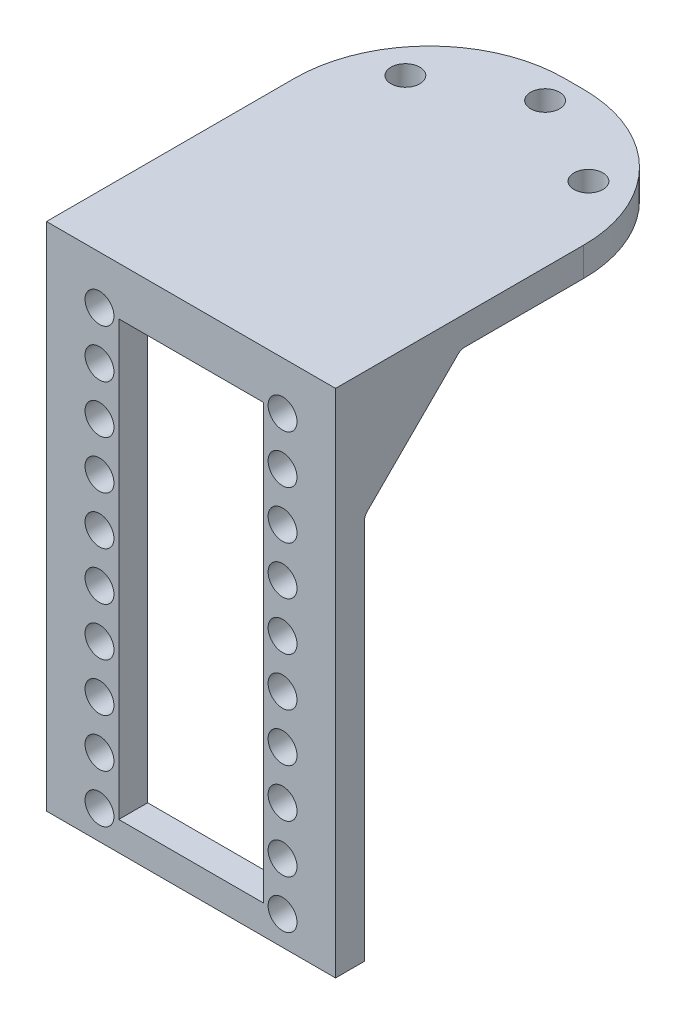
SolidWorks part; units mm, degrees
ref_plane "Front Plane" through (0, 0, 0) normal (0, 0, 1) x (1, 0, 0)
ref_plane "Top Plane" through (0, 0, 0) normal (0, 1, 0) x (1, 0, 0)
ref_plane "Right Plane" through (0, 0, 0) normal (1, 0, 0) x (0, 0, -1)
sketch "Sketch1" plane through (0, 0, 0) normal (1, 0, 0) x (0, 0, -1)
  line L0 (16.1753, 7.5418) -> (16.1753, 4.5418)
  line L1 (16.1753, 4.5418) -> (-15.8247, 4.5418)
  line L2 (-15.8247, 4.5418) -> (-15.8247, -45.4582)
  line L3 (-15.8247, -45.4582) -> (-18.8247, -45.4582)
  line L4 (-18.8247, -45.4582) -> (-18.8247, 7.5418)
  line L5 (-18.8247, 7.5418) -> (16.1753, 7.5418)
  dimension "D1" = 35
  dimension "D2" = 3
  dimension "D3" = 3
  dimension "D4" = 50
extrude "Boss-Extrude1" add sketch "Sketch1" against normal blind 30
sketch "Sketch2" plane through (0, 7.5418, 0) normal (0, 1, 0) x (1, 0, 0)
  line L0 (-30, 16.1753) -> (-30, -18.8247) construction
  line L1 (-30, 16.1753) -> (0, 16.1753) construction
  circle A0 centre (-5.5, 12.9253) radius 1.5
  circle A1 centre (-24.5, 12.9253) radius 1.5
  point P4 (0, 0)
  dimension "D1" = 3
  dimension "D2" = 19
  dimension "D3" = 5.5
  dimension "D4" = 3.25
extrude "Cut-Extrude1" cut sketch "Sketch2" against normal up to surface (3 mm away) up to face at (-15, 4.5418, -0.1753)
sketch "Sketch3" plane through (0, 0, 18.8247) normal (0, 0, 1) x (1, 0, 0)
  line L0 (-30, 7.5418) -> (-30, -45.4582) construction
  line L1 (-30, 7.5418) -> (0, 7.5418) construction
  line L2 (-30, -45.4582) -> (0, -45.4582) construction
  line L3 (-22.5, 2.5418) -> (-7.5, 2.5418)
  line L4 (-22.5, 2.5418) -> (-22.5, -42.4582)
  line L5 (-22.5, -42.4582) -> (-7.5, -42.4582)
  line L6 (-7.5, 2.5418) -> (-7.5, -42.4582)
  circle A0 centre (-24.5, 2.5418) radius 1.5
  circle A1 centre (-5.5, 2.5418) radius 1.5
  circle A2 centre (-24.5, -2.4582) radius 1.5
  circle A3 centre (-5.5, -2.4582) radius 1.5
  circle A4 centre (-24.5, -7.4582) radius 1.5
  circle A5 centre (-5.5, -7.4582) radius 1.5
  circle A6 centre (-24.5, -12.4582) radius 1.5
  circle A7 centre (-5.5, -12.4582) radius 1.5
  circle A8 centre (-24.5, -17.4582) radius 1.5
  circle A9 centre (-5.5, -17.4582) radius 1.5
  circle A10 centre (-24.5, -22.4582) radius 1.5
  circle A11 centre (-5.5, -22.4582) radius 1.5
  circle A12 centre (-24.5, -27.4582) radius 1.5
  circle A13 centre (-5.5, -27.4582) radius 1.5
  circle A14 centre (-24.5, -32.4582) radius 1.5
  circle A15 centre (-5.5, -32.4582) radius 1.5
  circle A16 centre (-24.5, -37.4582) radius 1.5
  circle A17 centre (-5.5, -37.4582) radius 1.5
  circle A18 centre (-24.5, -42.4582) radius 1.5
  circle A19 centre (-5.5, -42.4582) radius 1.5
  dimension "D1" = 3
  dimension "D2" = 19
  dimension "D3" = 5.5
  dimension "D4" = 5
  dimension "D6" = 15
  dimension "D7" = 2
  dimension "D8" = 45
  dimension "D9" = 3
  dimension "D5" = 10
extrude "Cut-Extrude2" cut sketch "Sketch3" against normal up to surface (3 mm away) up to face at (-15, -20.4582, 15.8247)
sketch "Sketch4" plane through (0, 0, -16.1753) normal (0, 0, -1) x (-1, 0, 0)
  line L1 (0, 4.5418) -> (30, 4.5418)
  line L2 (0, 4.5418) -> (0, 7.5418)
  line L3 (0, 7.5418) -> (30, 7.5418)
  line L4 (30, 4.5418) -> (30, 7.5418)
extrude "Boss-Extrude2" add sketch "Sketch4" along normal blind 4.75
sketch "Sketch5" plane through (0, 7.5418, 0) normal (0, 1, 0) x (1, 0, 0)
  line L2 (-30, 5.9253) -> (-30, 6.9253)
  line L3 (-16, 20.9253) -> (-14, 20.9253)
  line L5 (0, 6.9253) -> (0, 5.9253)
  line L6 (0, 20.9253) -> (0, -18.8247) construction
  circle A0 centre (-15, 17.9253) radius 1.5
  circle A5 centre (-24.5, 12.9253) radius 1.5 construction
  arc A6 (0, 6.9253) -> (-14, 20.9253) centre (-14, 6.9253) ccw
  arc A7 (-16, 20.9253) -> (-30, 6.9253) centre (-16, 6.9253) ccw
  point P8 (0, 20.9253)
  point P18 (-30, 20.9253)
  line M5 (0, -18.8247) -> (0, 20.9253)
  line M6 (0, 20.9253) -> (-30, 20.9253)
  line M7 (-30, 20.9253) -> (-30, -18.8247)
  dimension "D1" = 3
  dimension "D4" = 15
  dimension "D2" = 5
  dimension "D5" = 15
  dimension "D6" = 14
  dimension "D3" = 9.5
extrude "Cut-Extrude3" cut sketch "Sketch5" against normal up to surface (3 mm away) contours A7 M6 M7 | A0 | A6 M5 M6 region at (-3.1272, 7.5418, -17.7981) region at (-26.8728, 7.5418, -17.7981) region at (-15, 7.5418, -17.9253) up to face at (-5.5, 4.5418, -14.4253)
sketch "Sketch6" plane through (0, 0, 0) normal (1, 0, 0) x (0, 0, -1)
  line L0 (-15.8247, 4.5418) -> (-5.8247, 4.5418)
  line L1 (-15.8247, 4.5418) -> (6.9253, 4.5418) construction
  line L2 (-5.8247, 4.5418) -> (-15.8247, -5.4582)
  line L3 (-15.8247, -45.4582) -> (-15.8247, 4.5418) construction
  line L4 (-15.8247, -5.4582) -> (-15.8247, 4.5418)
  dimension "D1" = 10
  dimension "D2" = 10
extrude "Boss-Extrude3" add sketch "Sketch6" against normal blind 3
sketch "Sketch7" plane through (-30, 0, 0) normal (-1, 0, 0) x (0, 0, 1)
  line L5 (5.8247, 4.5418) -> (15.8247, -5.4582)
  line L6 (15.8247, -5.4582) -> (15.8247, 4.5418)
  line L7 (15.8247, 4.5418) -> (5.8247, 4.5418)
extrude "Boss-Extrude4" add sketch "Sketch7" against normal blind 3
fillet "Fillet1" radius 1 8 edges at (-3, 4.5418, 10.8247) (-3, -0.4582, 15.8247) (-1.5, -5.4582, 15.8247) (-1.5, 4.5418, 5.8247) (-28.5, 4.5418, 5.8247) (-27, 4.5418, 10.8247) (-27, -0.4582, 15.8247) (-28.5, -5.4582, 15.8247)
